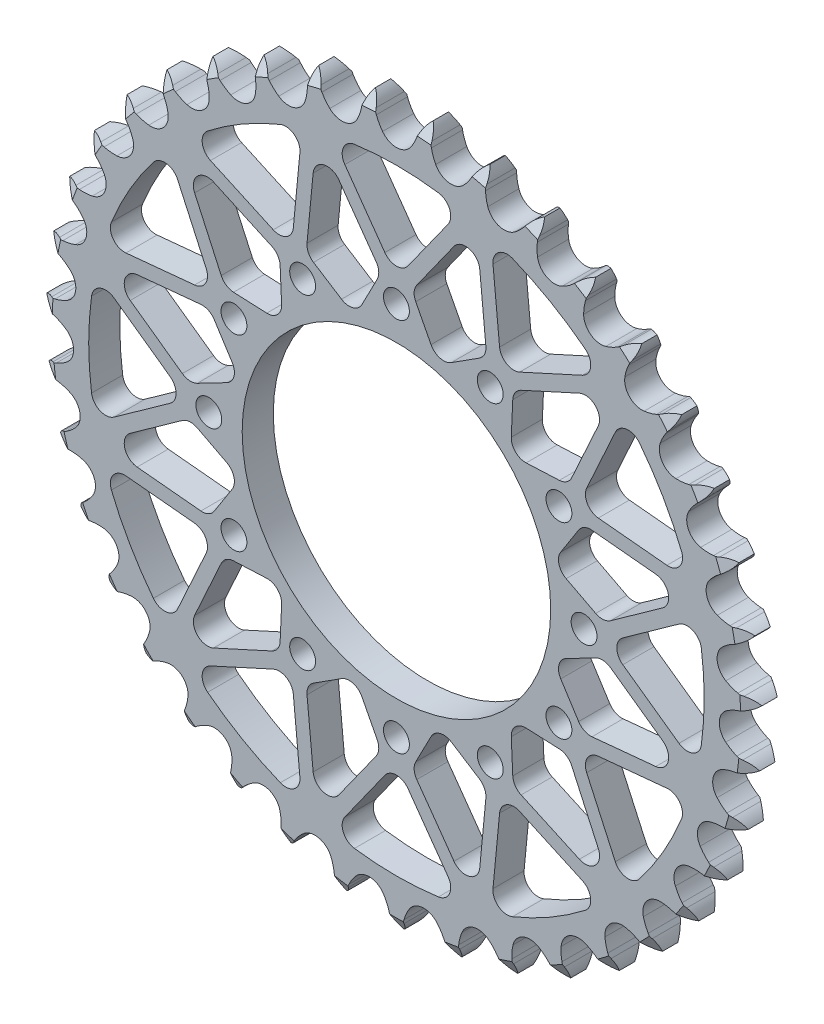
SolidWorks part; units mm, degrees
material "7075-T6 (SN)"
ref_plane "Front Plane" through (0, 0, 0) normal (0, 0, 1) x (1, 0, 0)
ref_plane "Top Plane" through (0, 0, 0) normal (0, 1, 0) x (1, 0, 0)
ref_plane "Right Plane" through (0, 0, 0) normal (1, 0, 0) x (0, 0, -1)
sketch "Work Sketch" plane through (0, 0, 0) normal (0, 0, 1) x (1, 0, 0)
  line L0 (0, 0) -> (0, 160.4542) construction
  line L1 (-112.0919, 78.9148) -> (87.2579, 78.9148) construction
  line L2 (5.102, 120.8822) -> (5.102, 112.9699) construction
  line L3 (-12.8497, 82.6953) -> (16.7256, 82.6953) construction
  line L4 (5.102, 82.6953) -> (-6.0879, 74.4036) construction
  line L5 (5.102, 82.6953) -> (-4.6505, 79.1506) construction
  line L6 (-4.6505, 79.1506) -> (-6.8863, 85.3019)
  line L7 (-11.5114, 78.0206) -> (-7.1525, 78.0206) construction
  line L8 (-11.0765, 124.7602) -> (-11.0765, 110.2345) construction
  line L9 (0, 0) -> (-3.4402, 42.6146) construction
  circle A0 centre (0, 0) radius 78.9148
  circle A1 centre (0, 78.9148) radius 4.0088
  arc A2 (-4.6505, 79.1506) -> (-3.2209, 76.5281) centre (5.0804, 82.7541) ccw
  circle A3 centre (-11.0765, 78.0206) radius 6.4254
  point P23 (-3.2209, 76.5281)
  dimension "D1" = 157.8295
  dimension "D8" = 10.3767
  dimension "D2" = 8.0177
  dimension "D3" = 5.102
  dimension "D4" = 3.7806
  dimension "D5" = 36.538
  dimension "D6" = 16.564
  dimension "D7" = 10.3767
  dimension "D9" = 0.8942
  dimension "D10" = 11.0765
  dimension "D11" = 4.615
sketch "Teeth Sketch" plane through (0, 0, 0) normal (0, 0, 1) x (1, 0, 0)
  line L0 (5.0376, 80.2155) -> (4.6505, 79.1506)
  line L1 (-7.4865, 92.7372) -> (-4.7839, 59.2593) construction
  line L2 (0, 0) -> (-10.9133, 132.3061) construction
  line L3 (7.8951, 79.9848) -> (8.1063, 78.8717)
  line L4 (16093.3137, -199351.4616) -> (-16096.7539, 199394.0762) construction
  line L5 (0, 146.3285) -> (0, 56.9858) construction
  line L6 (17.8398, 78.3686) -> (17.287, 77.3797)
  line L7 (0, -200000) -> (0, 200160.4542) construction
  line L8 (20.6234, 77.6826) -> (20.6533, 76.5499)
  line L9 (-4.6505, 79.1506) -> (-6.8863, 85.3019) construction
  line L10 (44.1616, 67.154) -> (43.8313, 66.0702)
  line L11 (-5.0376, 80.2155) -> (-4.6505, 79.1506)
  line L12 (30.18, 74.4921) -> (29.4757, 73.6046)
  line L13 (32.8175, 73.3684) -> (32.6653, 72.2456)
  line L14 (41.7385, 68.6862) -> (40.901, 67.9232)
  line L15 (52.2161, 61.1014) -> (51.267, 60.4826)
  line L16 (54.362, 59.2003) -> (53.8621, 58.1836)
  line L17 (61.3413, 51.9341) -> (60.3052, 51.4756)
  line L18 (63.1544, 49.7134) -> (62.4979, 48.79)
  line L19 (68.8777, 41.4218) -> (67.7815, 41.1354)
  line L20 (70.3112, 38.939) -> (69.515, 38.1328)
  line L21 (74.6303, 29.8366) -> (73.5023, 29.7298)
  line L22 (75.6469, 27.156) -> (74.7318, 26.488)
  line L23 (78.45, 17.4787) -> (77.3195, 17.5542)
  line L24 (79.0234, 14.6698) -> (78.013, 14.1572)
  line L25 (80.2378, 4.6681) -> (79.1341, 4.9239)
  line L26 (80.3533, 1.8035) -> (79.2737, 1.4597)
  line L27 (79.9476, -8.2634) -> (78.8992, -7.8338)
  line L28 (79.602, -11.1094) -> (78.4813, -11.2756)
  line L29 (77.5867, -20.9809) -> (76.6208, -20.3887)
  line L30 (76.7891, -23.7346) -> (75.6562, -23.7189)
  line L31 (73.2164, -33.155) -> (72.358, -32.4155)
  line L32 (71.9874, -35.7451) -> (70.8717, -35.5478)
  line L33 (66.9499, -44.4704) -> (66.2212, -43.6028)
  line L34 (65.3213, -46.8298) -> (64.2517, -46.4561)
  line L35 (58.9493, -54.634) -> (58.3693, -53.6608)
  line L36 (56.9634, -56.7016) -> (55.9676, -56.1612)
  line L37 (49.422, -63.3827) -> (49.0056, -62.329)
  line L38 (47.1301, -65.1049) -> (46.2339, -64.4118)
  line L39 (38.6147, -70.4897) -> (38.3727, -69.3829)
  line L40 (36.0763, -71.822) -> (35.3028, -70.9941)
  line L41 (26.8073, -75.7712) -> (26.746, -74.6398)
  line L42 (24.088, -76.679) -> (23.4574, -75.7377)
  line L43 (14.3056, -79.0901) -> (14.4266, -77.9636)
  line L44 (11.4759, -79.55) -> (11.0044, -78.5198)
  line L45 (1.4334, -80.3607) -> (1.7335, -79.2682)
  line L46 (-1.4334, -80.3607) -> (-1.7335, -79.2682)
  line L47 (-11.4759, -79.55) -> (-11.0044, -78.5198)
  line L48 (-14.3056, -79.0901) -> (-14.4266, -77.9636)
  line L49 (-24.088, -76.679) -> (-23.4574, -75.7377)
  line L50 (-26.8073, -75.7712) -> (-26.746, -74.6398)
  line L51 (-36.0763, -71.822) -> (-35.3028, -70.9941)
  line L52 (-38.6147, -70.4897) -> (-38.3727, -69.3829)
  line L53 (-47.1301, -65.1049) -> (-46.2339, -64.4118)
  line L54 (-49.422, -63.3827) -> (-49.0056, -62.329)
  line L55 (-56.9634, -56.7016) -> (-55.9676, -56.1612)
  line L56 (-58.9493, -54.634) -> (-58.3693, -53.6608)
  line L57 (-65.3213, -46.8298) -> (-64.2517, -46.4561)
  line L58 (-66.9499, -44.4704) -> (-66.2212, -43.6028)
  line L59 (-71.9874, -35.7451) -> (-70.8717, -35.5478)
  line L60 (-73.2164, -33.155) -> (-72.358, -32.4155)
  line L61 (-76.7891, -23.7346) -> (-75.6562, -23.7189)
  line L62 (-77.5867, -20.9809) -> (-76.6208, -20.3887)
  line L63 (-79.602, -11.1094) -> (-78.4813, -11.2756)
  line L64 (-79.9476, -8.2634) -> (-78.8992, -7.8338)
  line L65 (-80.3533, 1.8035) -> (-79.2737, 1.4597)
  line L66 (-80.2378, 4.6681) -> (-79.1341, 4.9239)
  line L67 (-79.0234, 14.6698) -> (-78.013, 14.1572)
  line L68 (-78.45, 17.4787) -> (-77.3195, 17.5542)
  line L69 (-75.6469, 27.156) -> (-74.7318, 26.488)
  line L70 (-74.6303, 29.8366) -> (-73.5023, 29.7298)
  line L71 (-70.3112, 38.939) -> (-69.515, 38.1328)
  line L72 (-68.8777, 41.4218) -> (-67.7815, 41.1354)
  line L73 (-63.1544, 49.7134) -> (-62.4979, 48.79)
  line L74 (-61.3413, 51.9341) -> (-60.3052, 51.4756)
  line L75 (-54.362, 59.2003) -> (-53.8621, 58.1836)
  line L76 (-52.2161, 61.1014) -> (-51.267, 60.4826)
  line L77 (-44.1616, 67.154) -> (-43.8313, 66.0702)
  line L78 (-41.7385, 68.6862) -> (-40.901, 67.9232)
  line L79 (-32.8175, 73.3684) -> (-32.6653, 72.2456)
  line L80 (-30.18, 74.4921) -> (-29.4757, 73.6046)
  line L81 (-20.6234, 77.6826) -> (-20.6533, 76.5499)
  line L82 (-17.8398, 78.3686) -> (-17.287, 77.3797)
  line L83 (-7.8951, 79.9848) -> (-8.1063, 78.8717)
  arc A0 (-6.8336, 82.8459) -> (-5.0376, 80.2155) centre (-11.0765, 78.0206) cw
  circle A1 centre (-11.0765, 78.0206) radius 6.4254 construction
  arc A2 (-3.2209, 76.5281) -> (-4.6505, 79.1506) centre (5.0804, 82.7541) cw
  arc A3 (-4.6505, 79.1506) -> (-3.2209, 76.5281) centre (5.0804, 82.7541) ccw construction
  circle A4 centre (0, 78.9148) radius 4.0088 construction
  arc A5 (-3.2209, 76.5281) -> (3.2209, 76.5281) centre (0, 78.9148) ccw
  arc A6 (3.2209, 76.5281) -> (4.6505, 79.1506) centre (-5.0804, 82.7541) ccw
  arc A7 (6.8336, 82.8459) -> (5.0376, 80.2155) centre (11.0765, 78.0206) ccw
  arc A8 (6.5443, 82.8692) -> (7.8951, 79.9848) centre (1.5824, 78.787) cw
  arc A9 (9.0967, 76.0537) -> (8.1063, 78.8717) centre (18.2893, 80.8676) cw
  arc A10 (9.0967, 76.0537) -> (15.4552, 75.0204) centre (12.6588, 77.8928) ccw
  arc A11 (15.4552, 75.0204) -> (17.287, 77.3797) centre (8.2601, 82.4975) ccw
  arc A12 (20.0345, 80.6769) -> (17.8398, 78.3686) centre (23.4484, 75.2334) ccw
  arc A13 (19.7528, 80.7463) -> (20.6234, 77.6826) centre (14.2002, 77.5129) cw
  arc A14 (21.1788, 73.6096) -> (20.6533, 76.5499) centre (31.0245, 76.8865) cw
  arc A15 (21.1788, 73.6096) -> (27.2892, 71.5697) centre (24.9898, 74.8535) ccw
  arc A16 (27.2892, 71.5697) -> (29.4757, 73.6046) centre (21.3867, 80.1041) ccw
  arc A17 (32.7165, 76.4184) -> (30.18, 74.4921) centre (35.2131, 70.4978) ccw
  arc A18 (32.4496, 76.5321) -> (32.8175, 73.3684) centre (26.4502, 74.2313) cw
  arc A19 (32.7124, 69.2591) -> (32.6653, 72.2456) centre (42.9562, 70.9142) cw
  arc A20 (32.7124, 69.2591) -> (38.4163, 66.2654) centre (36.6735, 69.8756) ccw
  arc A21 (38.4163, 66.2654) -> (40.901, 67.9232) centre (33.9593, 75.6361) ccw
  arc A22 (44.5512, 70.1807) -> (41.7385, 68.6862) centre (46.0657, 63.9363) ccw
  arc A23 (44.306, 70.3358) -> (44.1616, 67.154) centre (38.0153, 69.0271) cw
  arc A24 (43.3987, 63.1147) -> (43.8313, 66.0702) centre (53.7754, 63.1052) cw
  arc A25 (43.3987, 63.1147) -> (48.5486, 59.2448) centre (47.4074, 63.0878) ccw
  arc A26 (48.5486, 59.2448) -> (51.267, 60.4826) centre (45.6524, 69.2092) ccw
  arc A27 (55.2321, 62.1253) -> (52.2161, 61.1014) centre (55.7253, 55.7189) ccw
  arc A28 (55.0149, 62.3178) -> (54.362, 59.2003) centre (48.5957, 62.0351) cw
  arc A29 (52.961, 55.3358) -> (53.8621, 58.1836) centre (63.2018, 53.6618) cw
  arc A30 (52.961, 55.3358) -> (57.4234, 50.6899) centre (56.9135, 54.6662) ccw
  arc A31 (57.4234, 50.6899) -> (60.3052, 51.4756) centre (56.1632, 60.9898) ccw
  arc A32 (64.4824, 52.461) -> (61.3413, 51.9341) centre (63.9416, 46.0584) ccw
  arc A33 (64.2989, 52.6858) -> (63.1544, 49.7134) centre (57.9175, 53.4365) cw
  arc A34 (61.1517, 46.1237) -> (62.4979, 48.79) centre (70.9913, 42.8287) cw
  arc A35 (61.1517, 46.1237) -> (64.811, 40.8221) centre (64.9456, 44.8287) ccw
  arc A36 (64.811, 40.8221) -> (67.7815, 41.1354) centre (65.2193, 51.1908) ccw
  arc A37 (72.0627, 41.4379) -> (68.8777, 41.4218) centre (70.5018, 35.205) ccw
  arc A38 (71.9177, 41.6892) -> (70.3112, 38.939) centre (65.7393, 43.4539) cw
  arc A39 (67.7585, 35.717) -> (69.515, 38.1328) centre (76.9422, 30.8862) cw
  arc A40 (67.7585, 35.717) -> (70.5201, 29.8971) centre (71.2956, 33.8302) ccw
  arc A41 (70.5201, 29.8971) -> (73.5023, 29.7298) centre (72.5864, 40.0659) ccw
  arc A42 (77.7767, 29.3416) -> (74.6303, 29.8366) centre (75.2361, 23.4398) ccw
  arc A43 (77.6738, 29.6129) -> (75.6469, 27.156) centre (71.8585, 32.3458) cw
  arc A44 (72.6105, 24.3852) -> (74.7318, 26.488) centre (80.9003, 18.1439) cw
  arc A45 (72.6105, 24.3852) -> (74.4027, 18.1977) centre (75.7991, 21.9555) ccw
  arc A46 (74.4027, 18.1977) -> (77.3195, 17.5542) centre (78.0734, 27.9034) ccw
  arc A47 (81.4762, 16.4854) -> (78.45, 17.4787) centre (78.0218, 11.0675) ccw
  arc A48 (81.4182, 16.7697) -> (79.0234, 14.6698) centre (76.1166, 20.4) cw
  arc A49 (75.5818, 12.4219) -> (78.013, 14.1572) centre (82.7631, 4.9316) cw
  arc A50 (75.5818, 12.4219) -> (76.3583, 6.027) centre (78.3394, 9.5121) ccw
  arc A51 (76.3583, 6.027) -> (79.1341, 4.9239) centre (81.5384, 15.0182) ccw
  arc A52 (83.0656, 3.2022) -> (80.2378, 4.6681) centre (78.7868, -1.5914) ccw
  arc A53 (83.0539, 3.4922) -> (80.3533, 1.8035) centre (78.4033, 7.9259) cw
  arc A54 (76.5957, 0.1368) -> (79.2737, 1.4597) centre (82.4825, -8.4084) cw
  arc A55 (76.5957, 0.1368) -> (76.3363, -6.2998) centre (78.8508, -3.1776) ccw
  arc A56 (76.3363, -6.2998) -> (78.8992, -7.8338) centre (82.8916, 1.7441) ccw
  arc A57 (82.5035, -10.1639) -> (79.9476, -8.2634) centre (77.5113, -14.2091) ccw
  arc A58 (82.5385, -9.8758) -> (79.602, -11.1094) centre (78.6594, -4.7535) cw
  arc A59 (75.6257, -12.1517) -> (78.4813, -11.2756) centre (80.0655, -21.5307) cw
  arc A60 (75.6257, -12.1517) -> (74.3372, -18.4634) centre (77.3199, -15.785) ccw
  arc A61 (74.3372, -18.4634) -> (76.6208, -20.3887) centre (82.0979, -11.5753) ccw
  arc A62 (79.8047, -23.2668) -> (77.5867, -20.9809) centre (74.2283, -26.4587) ccw
  arc A63 (79.8855, -22.9881) -> (76.7891, -23.7346) centre (76.8783, -17.3098) cw
  arc A64 (72.6971, -24.1256) -> (75.6562, -23.7189) centre (75.5749, -34.0953) cw
  arc A65 (72.6971, -24.1256) -> (70.4128, -30.1488) centre (73.7866, -27.9836) ccw
  arc A66 (70.4128, -30.1488) -> (72.358, -32.4155) centre (79.178, -24.5948) ccw
  arc A67 (75.039, -35.7671) -> (73.2164, -33.155) centre (69.0227, -38.0232) ccw
  arc A68 (75.1634, -35.5049) -> (71.9874, -35.7451) centre (73.106, -29.4178) cw
  arc A69 (67.8857, -35.4746) -> (70.8717, -35.5478) centre (69.127, -45.7768) cw
  arc A70 (67.8857, -35.4746) -> (64.6648, -41.0534) centre (68.3422, -39.4574) ccw
  arc A71 (64.6648, -41.0534) -> (66.2212, -43.6028) centre (74.2074, -36.9773) ccw
  arc A72 (68.3299, -47.341) -> (66.9499, -44.4704) centre (62.0296, -48.6028) ccw
  arc A73 (68.4947, -47.1022) -> (65.3213, -46.8298) centre (67.4404, -40.7639) cw
  arc A74 (61.3161, -45.9049) -> (64.2517, -46.4561) centre (60.8887, -56.2728) cw
  arc A75 (61.3161, -45.9049) -> (57.2419, -50.8948) centre (61.1278, -49.9093) ccw
  arc A76 (57.2419, -50.8948) -> (58.3693, -53.6608) centre (67.3148, -48.4022) ccw
  arc A77 (59.851, -57.6888) -> (58.9493, -54.634) centre (53.4299, -57.9236) ccw
  arc A78 (60.052, -57.4796) -> (56.9634, -56.7016) centre (60.0281, -51.0542) cw
  arc A79 (53.1584, -55.1462) -> (55.9676, -56.1612) centre (51.0734, -65.3113) cw
  arc A80 (53.1584, -55.1462) -> (48.3366, -59.4179) centre (52.3302, -59.0685) ccw
  arc A81 (48.3366, -59.4179) -> (49.0056, -62.329) centre (58.6789, -58.5735) ccw
  arc A82 (49.822, -66.5425) -> (49.422, -63.3827) centre (43.4464, -65.7443) ccw
  arc A83 (50.054, -66.3682) -> (47.1301, -65.1049) centre (51.0611, -60.0222) cw
  arc A84 (43.6239, -62.9593) -> (46.2339, -64.4118) centre (39.9354, -72.6583) cw
  arc A85 (43.6239, -62.9593) -> (38.1793, -66.4022) centre (42.1772, -66.698) ccw
  arc A86 (38.1793, -66.4022) -> (38.3727, -69.3829) centre (48.5231, -67.2277) ccw
  arc A87 (38.5026, -73.6728) -> (38.6147, -70.4897) centre (32.3376, -71.8622) ccw
  arc A88 (38.7596, -73.538) -> (36.0763, -71.822) centre (40.7716, -67.4357) cw
  arc A89 (32.9596, -69.1417) -> (35.3028, -70.9941) centre (27.763, -78.1234) cw
  arc A90 (32.9596, -69.1417) -> (27.0333, -71.6667) centre (30.932, -72.6) ccw
  arc A91 (27.0333, -71.6667) -> (26.746, -74.6398) centre (37.1107, -74.1408) ccw
  arc A92 (26.1861, -78.8951) -> (26.8073, -75.7712) centre (20.3913, -76.1189) ccw
  arc A93 (26.4613, -78.8032) -> (24.088, -76.679) centre (29.4261, -73.1027) cw
  arc A94 (21.4417, -73.5335) -> (23.4574, -75.7377) centre (14.8716, -81.5653) cw
  arc A95 (21.4417, -73.5335) -> (15.187, -75.0751) centre (18.8855, -76.6216) ccw
  arc A96 (15.187, -75.0751) -> (14.4266, -77.9636) centre (24.7371, -79.1336) ccw
  arc A97 (13.1913, -82.0739) -> (14.3056, -79.0901) centre (7.9169, -78.4042) ccw
  arc A98 (13.4777, -82.0274) -> (11.4759, -79.55) centre (17.3186, -76.8763) cw
  arc A99 (9.3684, -76.0207) -> (11.0044, -78.5198) centre (1.595, -82.8946) cw
  arc A100 (9.3684, -76.0207) -> (2.9475, -76.5391) centre (6.35, -78.6589) ccw
  arc A101 (2.9475, -76.5391) -> (1.7335, -79.2682) centre (11.7228, -82.077) ccw
  arc A102 (-0.1451, -83.1271) -> (1.4334, -80.3607) centre (-4.7625, -78.6589) ccw
  arc A103 (0.1451, -83.1271) -> (-1.4334, -80.3607) centre (4.7625, -78.6589) cw
  arc A104 (-2.9475, -76.5391) -> (-1.7335, -79.2682) centre (-11.7228, -82.077) cw
  arc A105 (-2.9475, -76.5391) -> (-9.3684, -76.0207) centre (-6.35, -78.6589) ccw
  arc A106 (-9.3684, -76.0207) -> (-11.0044, -78.5198) centre (-1.595, -82.8946) ccw
  arc A107 (-13.4777, -82.0274) -> (-11.4759, -79.55) centre (-17.3186, -76.8763) ccw
  arc A108 (-13.1913, -82.0739) -> (-14.3056, -79.0901) centre (-7.9169, -78.4042) cw
  arc A109 (-15.187, -75.0751) -> (-14.4266, -77.9636) centre (-24.7371, -79.1336) cw
  arc A110 (-15.187, -75.0751) -> (-21.4417, -73.5335) centre (-18.8855, -76.6216) ccw
  arc A111 (-21.4417, -73.5335) -> (-23.4574, -75.7377) centre (-14.8716, -81.5653) ccw
  arc A112 (-26.4613, -78.8032) -> (-24.088, -76.679) centre (-29.4261, -73.1027) ccw
  arc A113 (-26.1861, -78.8951) -> (-26.8073, -75.7712) centre (-20.3913, -76.1189) cw
  arc A114 (-27.0333, -71.6667) -> (-26.746, -74.6398) centre (-37.1107, -74.1408) cw
  arc A115 (-27.0333, -71.6667) -> (-32.9596, -69.1417) centre (-30.932, -72.6) ccw
  arc A116 (-32.9596, -69.1417) -> (-35.3028, -70.9941) centre (-27.763, -78.1234) ccw
  arc A117 (-38.7596, -73.538) -> (-36.0763, -71.822) centre (-40.7716, -67.4357) ccw
  arc A118 (-38.5026, -73.6728) -> (-38.6147, -70.4897) centre (-32.3376, -71.8622) cw
  arc A119 (-38.1793, -66.4022) -> (-38.3727, -69.3829) centre (-48.5231, -67.2277) cw
  arc A120 (-38.1793, -66.4022) -> (-43.6239, -62.9593) centre (-42.1772, -66.698) ccw
  arc A121 (-43.6239, -62.9593) -> (-46.2339, -64.4118) centre (-39.9354, -72.6583) ccw
  arc A122 (-50.054, -66.3682) -> (-47.1301, -65.1049) centre (-51.0611, -60.0222) ccw
  arc A123 (-49.822, -66.5425) -> (-49.422, -63.3827) centre (-43.4464, -65.7443) cw
  arc A124 (-48.3366, -59.4179) -> (-49.0056, -62.329) centre (-58.6789, -58.5735) cw
  arc A125 (-48.3366, -59.4179) -> (-53.1584, -55.1462) centre (-52.3302, -59.0685) ccw
  arc A126 (-53.1584, -55.1462) -> (-55.9676, -56.1612) centre (-51.0734, -65.3113) ccw
  arc A127 (-60.052, -57.4796) -> (-56.9634, -56.7016) centre (-60.0281, -51.0542) ccw
  arc A128 (-59.851, -57.6888) -> (-58.9493, -54.634) centre (-53.4299, -57.9236) cw
  arc A129 (-57.2419, -50.8948) -> (-58.3693, -53.6608) centre (-67.3148, -48.4022) cw
  arc A130 (-57.2419, -50.8948) -> (-61.3161, -45.9049) centre (-61.1278, -49.9093) ccw
  arc A131 (-61.3161, -45.9049) -> (-64.2517, -46.4561) centre (-60.8887, -56.2728) ccw
  arc A132 (-68.4947, -47.1022) -> (-65.3213, -46.8298) centre (-67.4404, -40.7639) ccw
  arc A133 (-68.3299, -47.341) -> (-66.9499, -44.4704) centre (-62.0296, -48.6028) cw
  arc A134 (-64.6648, -41.0534) -> (-66.2212, -43.6028) centre (-74.2074, -36.9773) cw
  arc A135 (-64.6648, -41.0534) -> (-67.8857, -35.4746) centre (-68.3422, -39.4574) ccw
  arc A136 (-67.8857, -35.4746) -> (-70.8717, -35.5478) centre (-69.127, -45.7768) ccw
  arc A137 (-75.1634, -35.5049) -> (-71.9874, -35.7451) centre (-73.106, -29.4178) ccw
  arc A138 (-75.039, -35.7671) -> (-73.2164, -33.155) centre (-69.0227, -38.0232) cw
  arc A139 (-70.4128, -30.1488) -> (-72.358, -32.4155) centre (-79.178, -24.5948) cw
  arc A140 (-70.4128, -30.1488) -> (-72.6971, -24.1256) centre (-73.7866, -27.9836) ccw
  arc A141 (-72.6971, -24.1256) -> (-75.6562, -23.7189) centre (-75.5749, -34.0953) ccw
  arc A142 (-79.8855, -22.9881) -> (-76.7891, -23.7346) centre (-76.8783, -17.3098) ccw
  arc A143 (-79.8047, -23.2668) -> (-77.5867, -20.9809) centre (-74.2283, -26.4587) cw
  arc A144 (-74.3372, -18.4634) -> (-76.6208, -20.3887) centre (-82.0979, -11.5753) cw
  arc A145 (-74.3372, -18.4634) -> (-75.6257, -12.1517) centre (-77.3199, -15.785) ccw
  arc A146 (-75.6257, -12.1517) -> (-78.4813, -11.2756) centre (-80.0655, -21.5307) ccw
  arc A147 (-82.5385, -9.8758) -> (-79.602, -11.1094) centre (-78.6594, -4.7535) ccw
  arc A148 (-82.5035, -10.1639) -> (-79.9476, -8.2634) centre (-77.5113, -14.2091) cw
  arc A149 (-76.3363, -6.2998) -> (-78.8992, -7.8338) centre (-82.8916, 1.7441) cw
  arc A150 (-76.3363, -6.2998) -> (-76.5957, 0.1368) centre (-78.8508, -3.1776) ccw
  arc A151 (-76.5957, 0.1368) -> (-79.2737, 1.4597) centre (-82.4825, -8.4084) ccw
  arc A152 (-83.0539, 3.4922) -> (-80.3533, 1.8035) centre (-78.4033, 7.9259) ccw
  arc A153 (-83.0656, 3.2022) -> (-80.2378, 4.6681) centre (-78.7868, -1.5914) cw
  arc A154 (-76.3583, 6.027) -> (-79.1341, 4.9239) centre (-81.5384, 15.0182) cw
  arc A155 (-76.3583, 6.027) -> (-75.5818, 12.4219) centre (-78.3394, 9.5121) ccw
  arc A156 (-75.5818, 12.4219) -> (-78.013, 14.1572) centre (-82.7631, 4.9316) ccw
  arc A157 (-81.4182, 16.7697) -> (-79.0234, 14.6698) centre (-76.1166, 20.4) ccw
  arc A158 (-81.4762, 16.4854) -> (-78.45, 17.4787) centre (-78.0218, 11.0675) cw
  arc A159 (-74.4027, 18.1977) -> (-77.3195, 17.5542) centre (-78.0734, 27.9034) cw
  arc A160 (-74.4027, 18.1977) -> (-72.6105, 24.3852) centre (-75.7991, 21.9555) ccw
  arc A161 (-72.6105, 24.3852) -> (-74.7318, 26.488) centre (-80.9003, 18.1439) ccw
  arc A162 (-77.6738, 29.6129) -> (-75.6469, 27.156) centre (-71.8585, 32.3458) ccw
  arc A163 (-77.7767, 29.3416) -> (-74.6303, 29.8366) centre (-75.2361, 23.4398) cw
  arc A164 (-70.5201, 29.8971) -> (-73.5023, 29.7298) centre (-72.5864, 40.0659) cw
  arc A165 (-70.5201, 29.8971) -> (-67.7585, 35.717) centre (-71.2956, 33.8302) ccw
  arc A166 (-67.7585, 35.717) -> (-69.515, 38.1328) centre (-76.9422, 30.8862) ccw
  arc A167 (-71.9177, 41.6892) -> (-70.3112, 38.939) centre (-65.7393, 43.4539) ccw
  arc A168 (-72.0627, 41.4379) -> (-68.8777, 41.4218) centre (-70.5018, 35.205) cw
  arc A169 (-64.811, 40.8221) -> (-67.7815, 41.1354) centre (-65.2193, 51.1908) cw
  arc A170 (-64.811, 40.8221) -> (-61.1517, 46.1237) centre (-64.9456, 44.8287) ccw
  arc A171 (-61.1517, 46.1237) -> (-62.4979, 48.79) centre (-70.9913, 42.8287) ccw
  arc A172 (-64.2989, 52.6858) -> (-63.1544, 49.7134) centre (-57.9175, 53.4365) ccw
  arc A173 (-64.4824, 52.461) -> (-61.3413, 51.9341) centre (-63.9416, 46.0584) cw
  arc A174 (-57.4234, 50.6899) -> (-60.3052, 51.4756) centre (-56.1632, 60.9898) cw
  arc A175 (-57.4234, 50.6899) -> (-52.961, 55.3358) centre (-56.9135, 54.6662) ccw
  arc A176 (-52.961, 55.3358) -> (-53.8621, 58.1836) centre (-63.2018, 53.6618) ccw
  arc A177 (-55.0149, 62.3178) -> (-54.362, 59.2003) centre (-48.5957, 62.0351) ccw
  arc A178 (-55.2321, 62.1253) -> (-52.2161, 61.1014) centre (-55.7253, 55.7189) cw
  arc A179 (-48.5486, 59.2448) -> (-51.267, 60.4826) centre (-45.6524, 69.2092) cw
  arc A180 (-48.5486, 59.2448) -> (-43.3987, 63.1147) centre (-47.4074, 63.0878) ccw
  arc A181 (-43.3987, 63.1147) -> (-43.8313, 66.0702) centre (-53.7754, 63.1052) ccw
  arc A182 (-44.306, 70.3358) -> (-44.1616, 67.154) centre (-38.0153, 69.0271) ccw
  arc A183 (-44.5512, 70.1807) -> (-41.7385, 68.6862) centre (-46.0657, 63.9363) cw
  arc A184 (-38.4163, 66.2654) -> (-40.901, 67.9232) centre (-33.9593, 75.6361) cw
  arc A185 (-38.4163, 66.2654) -> (-32.7124, 69.2591) centre (-36.6735, 69.8756) ccw
  arc A186 (-32.7124, 69.2591) -> (-32.6653, 72.2456) centre (-42.9562, 70.9142) ccw
  arc A187 (-32.4496, 76.5321) -> (-32.8175, 73.3684) centre (-26.4502, 74.2313) ccw
  arc A188 (-32.7165, 76.4184) -> (-30.18, 74.4921) centre (-35.2131, 70.4978) cw
  arc A189 (-27.2892, 71.5697) -> (-29.4757, 73.6046) centre (-21.3867, 80.1041) cw
  arc A190 (-27.2892, 71.5697) -> (-21.1788, 73.6096) centre (-24.9898, 74.8535) ccw
  arc A191 (-21.1788, 73.6096) -> (-20.6533, 76.5499) centre (-31.0245, 76.8865) ccw
  arc A192 (-19.7528, 80.7463) -> (-20.6234, 77.6826) centre (-14.2002, 77.5129) ccw
  arc A193 (-20.0345, 80.6769) -> (-17.8398, 78.3686) centre (-23.4484, 75.2334) cw
  arc A194 (-15.4552, 75.0204) -> (-17.287, 77.3797) centre (-8.2601, 82.4975) cw
  arc A195 (-15.4552, 75.0204) -> (-9.0967, 76.0537) centre (-12.6588, 77.8928) ccw
  arc A196 (-9.0967, 76.0537) -> (-8.1063, 78.8717) centre (-18.2893, 80.8676) ccw
  arc A197 (-6.5443, 82.8692) -> (-7.8951, 79.9848) centre (-1.5824, 78.787) ccw
  point P77 (0, 0)
  dimension "D1" = 4.615
  dimension "D2" = 4.715
  dimension "D3" = 39
extrude "Extrusion" add sketch "Teeth Sketch" along normal blind 7.2136 contours A0 region at (0, 0, 0)
sketch "Sketch1" plane through (0, 0, 0) normal (0, 0, -1) x (-1, 0, 0)
  circle A0 centre (0, 0) radius 78.9443
  circle A1 centre (0, 0) radius 35.7643
  dimension "D1" = 43.18
extrude "Cut-Extrude" cut sketch "Sketch1" against normal through all both and the other way through all contours A1
ref_axis "Axis2" through (0, 0, -0.3607) along (0, 0, 1)
ref_axis "Axis1" [suppressed] through (0, 0, 7.2136) along (0, 0, -1)
ref_plane "Sprocket Center Plane" through (0, 0, 3.6068) normal (0, 0, 1) x (1, 0, 0)
sketch "Pitch Circle" plane through (0, 0, 3.6068) normal (0, 0, -1) x (-1, 0, 0)
  circle A0 centre (0, 0) radius 82.9531 construction
  dimension "D1" = 165.9063
sketch "Chain Pitch Circle" plane through (0, 0, 0) normal (0, 0, -1) x (-1, 0, 0)
  circle A0 centre (0, 0) radius 82.9531 construction
  dimension "D1" = 165.9063
ref_plane "Center Plane" through (0, 0, 3.6068) normal (0, 0, 1) x (1, 0, 0)
hole_wizard "Ø6.0mm Dowel Hole1" positions "Sketch7" profile "Sketch8" hole size "Ø6.0" standard "ANSI Metric" end condition through all
sketch "Sketch7" plane through (0, 0, 7.2136) normal (0, 0, 1) x (1, 0, 0)
  point P0 (-43.5, 0)
  dimension "D1" = 43.5
sketch "Sketch8" plane through (-43.5, 0, 7.2136) normal (1, 0, 0) x (0, -1, 0)
  line L0 (0, 0) -> (0, 7.2136)
  line L1 (0, 7.2136) -> (3, 7.2136)
  line L2 (3, 7.2136) -> (3, 0)
  line L5 (3, 0) -> (0, 0)
  line L11 (0, -6.35) -> (0, 107.95) construction
  dimension "Thru Hole Dia." = 6
  dimension "Thru Hole Depth" = 7.2136
pattern_circular "CirPattern1" count 12 over 360 about axis through (0, 0, 7.2136) along (0, 0, -1) of "Ø6.0mm Dowel Hole1" reverse direction yes
ref_plane "Plane1" through (0, 0, 3.6068) normal (0, 0, -1) x (-1, 0, 0)
sketch "Sketch9" plane through (0, 0, 0) normal (0, 0, 1) x (1, 0, 0)
  line L0 (-43.5, 0) -> (-71.3499, 0) construction
  line L1 (-69.7539, 15.0068) -> (-48.707, 0)
  line L2 (-69.7539, -15.0068) -> (-48.707, 0)
  line L11 (-43.5, 0) -> (-37.6721, 21.75) construction
  line L13 (-68.9187, 18.4667) -> (-36.1404, 9.6838) construction
  line L18 (-43.3252, 20.9264) -> (-36.1404, 9.6838)
  line L19 (-47.9839, 3.5399) -> (-36.1404, 9.6838)
  line L20 (-43.3252, 20.9264) -> (-68.9187, 18.4667)
  line L21 (-47.9839, 3.5399) -> (-68.9187, 18.4667)
  circle A0 centre (0, 0) radius 74.9059 construction
  arc A1 (-57.4234, 50.6899) -> (-52.961, 55.3358) centre (-56.9135, 54.6662) ccw construction
  circle A2 centre (-43.5, 0) radius 3 construction
  circle A3 centre (-43.5, 0) radius 5.207
  circle A4 centre (-37.6721, 21.75) radius 3 construction
  circle A6 centre (-37.6721, 21.75) radius 5.207
  circle A196 centre (0, 0) radius 71.3499
  circle A197 centre (0, 0) radius 35.7643 construction
  circle A198 centre (0, 0) radius 35.7643
  circle A199 centre (0, 0) radius 37.4153 construction
  point P17 (-40.5861, 10.875)
  dimension "D1" = 3.556
  dimension "D2" = 1.651
  dimension "D3" = 10.414
  dimension "D4" = 3.302
extrude "Cut-Extrude2" cut sketch "Sketch9" along normal through all contours L1 A196 L2 | L21 L19 L18 L20 region at (-63.4426, 0, 0) region at (-50.2379, 13.4612, 0)
fillet "Fillet2" radius 3.302 7 edges at (-68.9187, 18.4667, 3.6068) (-36.1404, 9.6838, 3.6068) (-47.9839, 3.5399, 3.6068) (-43.3252, 20.9264, 3.6068) (-69.7539, -15.0068, 3.6068) (-48.707, 0, 3.6068) (-69.7539, 15.0068, 3.6068)
pattern_circular "CirPattern3" count 12 over 360 about axis through (0, 0, 7.2136) along (0, 0, -1) of "Cut-Extrude2", "Fillet2"
sketch "Sketch14" plane through (0, 0, 7.2136) normal (0, 0, 1) x (1, 0, 0)
  line L0 (-46.191, -4.47) -> (-39.3483, -8.0197) construction
  line L1 (-38.2956, 5.9905) -> (-37.9766, 6.1559)
  line L2 (-43.5, 0) -> (-38.293, 0) construction
  line L3 (-38.2956, -5.9905) -> (-37.9766, -6.1559)
  line L4 (-30.1697, 24.3357) -> (-29.8108, 24.3195)
  line L5 (-36.1602, 13.9599) -> (-35.9667, 13.6571)
  line L6 (-13.9599, 36.1602) -> (-13.6571, 35.9667)
  line L7 (-24.3357, 30.1697) -> (-24.3195, 29.8108)
  line L8 (5.9905, 38.2956) -> (6.1559, 37.9766)
  line L9 (-5.9905, 38.2956) -> (-6.1559, 37.9766)
  line L10 (24.3357, 30.1697) -> (24.3195, 29.8108)
  line L11 (13.9599, 36.1602) -> (13.6571, 35.9667)
  line L12 (36.1602, 13.9599) -> (35.9667, 13.6571)
  line L13 (30.1697, 24.3357) -> (29.8108, 24.3195)
  line L14 (38.2956, -5.9905) -> (37.9766, -6.1559)
  line L15 (38.2956, 5.9905) -> (37.9766, 6.1559)
  line L16 (30.1697, -24.3357) -> (29.8108, -24.3195)
  line L17 (36.1602, -13.9599) -> (35.9667, -13.6571)
  line L18 (13.9599, -36.1602) -> (13.6571, -35.9667)
  line L19 (24.3357, -30.1697) -> (24.3195, -29.8108)
  line L20 (-5.9905, -38.2956) -> (-6.1559, -37.9766)
  line L21 (5.9905, -38.2956) -> (6.1559, -37.9766)
  line L22 (-24.3357, -30.1697) -> (-24.3195, -29.8108)
  line L23 (-13.9599, -36.1602) -> (-13.6571, -35.9667)
  line L24 (-36.1602, -13.9599) -> (-35.9667, -13.6571)
  line L25 (-30.1697, -24.3357) -> (-29.8108, -24.3195)
  arc A0 (-39.0014, -2.6222) -> (-39.0014, 2.6222) centre (-43.5, 0) ccw
  circle A1 centre (0, 0) radius 35.7643 construction
  arc A2 (-37.9766, -6.1559) -> (-39.0014, -2.6222) centre (-36.807, -3.9013) cw
  arc A3 (-38.2956, 5.9905) -> (-36.1602, 13.9599) centre (-40.8688, 10.9508) ccw
  arc A4 (-38.2956, 5.9905) -> (-36.1602, 13.9599) centre (-40.8688, 10.9508) ccw
  arc A5 (-37.9766, 6.1559) -> (-39.0014, 2.6222) centre (-36.807, 3.9013) ccw
  circle A6 centre (0, 0) radius 35.7643
  arc A7 (-30.1697, 24.3357) -> (-24.3357, 30.1697) centre (-29.918, 29.918) ccw
  arc A8 (-29.8108, 24.3195) -> (-32.4651, 21.7716) centre (-29.9252, 21.7821) ccw
  arc A9 (-35.0873, 17.2299) -> (-32.4651, 21.7716) centre (-37.6721, 21.75) ccw
  arc A10 (-35.9667, 13.6571) -> (-35.0873, 17.2299) centre (-33.8264, 15.0249) cw
  arc A11 (-13.9599, 36.1602) -> (-5.9905, 38.2956) centre (-10.9508, 40.8688) ccw
  arc A12 (-13.6571, 35.9667) -> (-17.2299, 35.0873) centre (-15.0249, 33.8264) ccw
  arc A13 (-21.7716, 32.4651) -> (-17.2299, 35.0873) centre (-21.75, 37.6721) ccw
  arc A14 (-24.3195, 29.8108) -> (-21.7716, 32.4651) centre (-21.7821, 29.9252) cw
  arc A15 (5.9905, 38.2956) -> (13.9599, 36.1602) centre (10.9508, 40.8688) ccw
  arc A16 (6.1559, 37.9766) -> (2.6222, 39.0014) centre (3.9013, 36.807) ccw
  arc A17 (-2.6222, 39.0014) -> (2.6222, 39.0014) centre (0, 43.5) ccw
  arc A18 (-6.1559, 37.9766) -> (-2.6222, 39.0014) centre (-3.9013, 36.807) cw
  arc A19 (24.3357, 30.1697) -> (30.1697, 24.3357) centre (29.918, 29.918) ccw
  arc A20 (24.3195, 29.8108) -> (21.7716, 32.4651) centre (21.7821, 29.9252) ccw
  arc A21 (17.2299, 35.0873) -> (21.7716, 32.4651) centre (21.75, 37.6721) ccw
  arc A22 (13.6571, 35.9667) -> (17.2299, 35.0873) centre (15.0249, 33.8264) cw
  arc A23 (36.1602, 13.9599) -> (38.2956, 5.9905) centre (40.8688, 10.9508) ccw
  arc A24 (35.9667, 13.6571) -> (35.0873, 17.2299) centre (33.8264, 15.0249) ccw
  arc A25 (32.4651, 21.7716) -> (35.0873, 17.2299) centre (37.6721, 21.75) ccw
  arc A26 (29.8108, 24.3195) -> (32.4651, 21.7716) centre (29.9252, 21.7821) cw
  arc A27 (38.2956, -5.9905) -> (36.1602, -13.9599) centre (40.8688, -10.9508) ccw
  arc A28 (37.9766, -6.1559) -> (39.0014, -2.6222) centre (36.807, -3.9013) ccw
  arc A29 (39.0014, 2.6222) -> (39.0014, -2.6222) centre (43.5, 0) ccw
  arc A30 (37.9766, 6.1559) -> (39.0014, 2.6222) centre (36.807, 3.9013) cw
  arc A31 (30.1697, -24.3357) -> (24.3357, -30.1697) centre (29.918, -29.918) ccw
  arc A32 (29.8108, -24.3195) -> (32.4651, -21.7716) centre (29.9252, -21.7821) ccw
  arc A33 (35.0873, -17.2299) -> (32.4651, -21.7716) centre (37.6721, -21.75) ccw
  arc A34 (35.9667, -13.6571) -> (35.0873, -17.2299) centre (33.8264, -15.0249) cw
  arc A35 (13.9599, -36.1602) -> (5.9905, -38.2956) centre (10.9508, -40.8688) ccw
  arc A36 (13.6571, -35.9667) -> (17.2299, -35.0873) centre (15.0249, -33.8264) ccw
  arc A37 (21.7716, -32.4651) -> (17.2299, -35.0873) centre (21.75, -37.6721) ccw
  arc A38 (24.3195, -29.8108) -> (21.7716, -32.4651) centre (21.7821, -29.9252) cw
  arc A39 (-5.9905, -38.2956) -> (-13.9599, -36.1602) centre (-10.9508, -40.8688) ccw
  arc A40 (-6.1559, -37.9766) -> (-2.6222, -39.0014) centre (-3.9013, -36.807) ccw
  arc A41 (2.6222, -39.0014) -> (-2.6222, -39.0014) centre (0, -43.5) ccw
  arc A42 (6.1559, -37.9766) -> (2.6222, -39.0014) centre (3.9013, -36.807) cw
  arc A43 (-24.3357, -30.1697) -> (-30.1697, -24.3357) centre (-29.918, -29.918) ccw
  arc A44 (-24.3195, -29.8108) -> (-21.7716, -32.4651) centre (-21.7821, -29.9252) ccw
  arc A45 (-17.2299, -35.0873) -> (-21.7716, -32.4651) centre (-21.75, -37.6721) ccw
  arc A46 (-13.6571, -35.9667) -> (-17.2299, -35.0873) centre (-15.0249, -33.8264) cw
  arc A47 (-36.1602, -13.9599) -> (-38.2956, -5.9905) centre (-40.8688, -10.9508) ccw
  arc A48 (-35.9667, -13.6571) -> (-35.0873, -17.2299) centre (-33.8264, -15.0249) ccw
  arc A49 (-32.4651, -21.7716) -> (-35.0873, -17.2299) centre (-37.6721, -21.75) ccw
  arc A50 (-29.8108, -24.3195) -> (-32.4651, -21.7716) centre (-29.9252, -21.7821) cw
  point P10 (-41.0188, -4.5778)
  point P16 (-41.0188, 4.5778)
  point P144 (0, 0)
  dimension "D2" = 2.54
  dimension "D1" = 2.286
  dimension "D3" = 12
extrude "Cut-Extrude7" [suppressed] cut sketch "Sketch14" against normal through all
sketch "Sketch15" plane through (0, 0, 0) normal (0, 0, -1) x (-1, 0, 0)
  line L9 (-38.264, 54.1071) -> (-28.7286, 49.7594)
  line L10 (-28.7286, 49.7594) -> (-27.7261, 60.1911)
  line L11 (-49.7594, 28.7286) -> (-54.1071, 38.264)
  line L12 (-60.1911, 27.7261) -> (-49.7594, 28.7286)
  line L13 (-49.7594, 28.7286) -> (-54.1071, 38.264)
  line L14 (-60.1911, 27.7261) -> (-49.7594, 28.7286)
  line L15 (-47.5649, 9.4801) -> (-43.4148, 11.633)
  line L16 (-54.9005, 14.7105) -> (-47.5649, 9.4801)
  line L17 (-45.9324, 15.5724) -> (-54.9005, 14.7105)
  line L18 (-43.4148, 11.633) -> (-45.9324, 15.5724)
  line L19 (-47.5649, 9.4801) -> (-43.4148, 11.633)
  line L20 (-54.9005, 14.7105) -> (-47.5649, 9.4801)
  line L21 (-45.9324, 15.5724) -> (-54.9005, 14.7105)
  line L22 (-43.4148, 11.633) -> (-45.9324, 15.5724)
  line L23 (-40.1899, 40.1899) -> (-36.4523, 31.9925)
  line L24 (-36.4523, 31.9925) -> (-31.7819, 31.7819)
  line L25 (-31.7819, 31.7819) -> (-31.9925, 36.4523)
  line L26 (-31.9925, 36.4523) -> (-40.1899, 40.1899)
  line L27 (-6.084, 65.9901) -> (0, 57.4573)
  line L28 (0, 57.4573) -> (6.084, 65.9901)
  line L29 (-14.7105, 54.9005) -> (-15.5724, 45.9324)
  line L30 (-15.5724, 45.9324) -> (-11.633, 43.4148)
  line L31 (-11.633, 43.4148) -> (-9.4801, 47.5649)
  line L32 (-9.4801, 47.5649) -> (-14.7105, 54.9005)
  line L33 (27.7261, 60.1911) -> (28.7286, 49.7594)
  line L34 (28.7286, 49.7594) -> (38.264, 54.1071)
  line L35 (14.7105, 54.9005) -> (9.4801, 47.5649)
  line L36 (9.4801, 47.5649) -> (11.633, 43.4148)
  line L37 (11.633, 43.4148) -> (15.5724, 45.9324)
  line L38 (15.5724, 45.9324) -> (14.7105, 54.9005)
  line L39 (54.1071, 38.264) -> (49.7594, 28.7286)
  line L40 (49.7594, 28.7286) -> (60.1911, 27.7261)
  line L41 (40.1899, 40.1899) -> (31.9925, 36.4523)
  line L42 (31.9925, 36.4523) -> (31.7819, 31.7819)
  line L43 (31.7819, 31.7819) -> (36.4523, 31.9925)
  line L44 (36.4523, 31.9925) -> (40.1899, 40.1899)
  line L45 (65.9901, 6.084) -> (57.4573, 0)
  line L46 (57.4573, 0) -> (65.9901, -6.084)
  line L47 (54.9005, 14.7105) -> (45.9324, 15.5724)
  line L48 (45.9324, 15.5724) -> (43.4148, 11.633)
  line L49 (43.4148, 11.633) -> (47.5649, 9.4801)
  line L50 (47.5649, 9.4801) -> (54.9005, 14.7105)
  line L51 (60.1911, -27.7261) -> (49.7594, -28.7286)
  line L52 (49.7594, -28.7286) -> (54.1071, -38.264)
  line L53 (54.9005, -14.7105) -> (47.5649, -9.4801)
  line L54 (47.5649, -9.4801) -> (43.4148, -11.633)
  line L55 (43.4148, -11.633) -> (45.9324, -15.5724)
  line L56 (45.9324, -15.5724) -> (54.9005, -14.7105)
  line L57 (38.264, -54.1071) -> (28.7286, -49.7594)
  line L58 (28.7286, -49.7594) -> (27.7261, -60.1911)
  line L59 (40.1899, -40.1899) -> (36.4523, -31.9925)
  line L60 (36.4523, -31.9925) -> (31.7819, -31.7819)
  line L61 (31.7819, -31.7819) -> (31.9925, -36.4523)
  line L62 (31.9925, -36.4523) -> (40.1899, -40.1899)
  line L63 (6.084, -65.9901) -> (0, -57.4573)
  line L64 (0, -57.4573) -> (-6.084, -65.9901)
  line L65 (14.7105, -54.9005) -> (15.5724, -45.9324)
  line L66 (15.5724, -45.9324) -> (11.633, -43.4148)
  line L67 (11.633, -43.4148) -> (9.4801, -47.5649)
  line L68 (9.4801, -47.5649) -> (14.7105, -54.9005)
  line L69 (-27.7261, -60.1911) -> (-28.7286, -49.7594)
  line L70 (-28.7286, -49.7594) -> (-38.264, -54.1071)
  line L71 (-14.7105, -54.9005) -> (-9.4801, -47.5649)
  line L72 (-9.4801, -47.5649) -> (-11.633, -43.4148)
  line L73 (-11.633, -43.4148) -> (-15.5724, -45.9324)
  line L74 (-15.5724, -45.9324) -> (-14.7105, -54.9005)
  line L75 (-54.1071, -38.264) -> (-49.7594, -28.7286)
  line L76 (-49.7594, -28.7286) -> (-60.1911, -27.7261)
  line L77 (-40.1899, -40.1899) -> (-31.9925, -36.4523)
  line L78 (-31.9925, -36.4523) -> (-31.7819, -31.7819)
  line L79 (-31.7819, -31.7819) -> (-36.4523, -31.9925)
  line L80 (-36.4523, -31.9925) -> (-40.1899, -40.1899)
  line L81 (-65.9901, -6.084) -> (-57.4573, 0)
  line L82 (-57.4573, 0) -> (-65.9901, 6.084)
  line L83 (-54.9005, -14.7105) -> (-45.9324, -15.5724)
  line L84 (-45.9324, -15.5724) -> (-43.4148, -11.633)
  line L85 (-43.4148, -11.633) -> (-47.5649, -9.4801)
  line L86 (-47.5649, -9.4801) -> (-54.9005, -14.7105)
  circle A13 centre (0, 0) radius 31.6425
  arc A18 (-27.7261, 60.1911) -> (-38.264, 54.1071) centre (0, 0) ccw
  arc A19 (6.084, 65.9901) -> (-6.084, 65.9901) centre (0, 0) ccw
  arc A20 (38.264, 54.1071) -> (27.7261, 60.1911) centre (0, 0) ccw
  arc A21 (60.1911, 27.7261) -> (54.1071, 38.264) centre (0, 0) ccw
  arc A22 (-54.1071, 38.264) -> (-60.1911, 27.7261) centre (0, 0) ccw
  arc A23 (-54.1071, 38.264) -> (-60.1911, 27.7261) centre (0, 0) ccw
  arc A24 (65.9901, -6.084) -> (65.9901, 6.084) centre (0, 0) ccw
  arc A25 (54.1071, -38.264) -> (60.1911, -27.7261) centre (0, 0) ccw
  arc A26 (27.7261, -60.1911) -> (38.264, -54.1071) centre (0, 0) ccw
  arc A27 (-6.084, -65.9901) -> (6.084, -65.9901) centre (0, 0) ccw
  arc A28 (-38.264, -54.1071) -> (-27.7261, -60.1911) centre (0, 0) ccw
  arc A29 (-60.1911, -27.7261) -> (-54.1071, -38.264) centre (0, 0) ccw
  arc A30 (-65.9901, 6.084) -> (-65.9901, -6.084) centre (0, 0) ccw
  point P3 (0, 0)
  point P28 (0, 0)
  point P123 (0, 0)
  dimension "D6" = 5.08
  dimension "D7" = 5.08
  dimension "D8" = 12
sketch "Sketch16" plane through (0, 0, 0) normal (0, 0, -1) x (-1, 0, 0)
  line L1 (88.9, 88.9) -> (-88.9, 88.9)
  line L2 (88.9, 88.9) -> (88.9, -88.9)
  line L3 (88.9, -88.9) -> (-88.9, -88.9)
  line L4 (-88.9, 88.9) -> (-88.9, -88.9)
  line L5 (88.9, 88.9) -> (-88.9, -88.9) construction
  line L6 (88.9, -88.9) -> (-88.9, 88.9) construction
  point P0 (0, 0)
  dimension "D1" = 177.8
  dimension "D2" = 177.8
sketch "Sketch17" plane through (0, 0, 0) normal (0, 0, -1) x (-1, 0, 0)
  line L0 (88.9, 88.9) -> (-88.9, -88.9) construction
  line L2 (88.9, -88.9) -> (-88.9, -88.9)
  line L3 (88.9, -88.9) -> (88.9, 88.9)
  line L4 (88.9, 88.9) -> (-88.9, 88.9)
  line L5 (-88.9, -88.9) -> (-88.9, 88.9)
  line L6 (88.9, -88.9) -> (-88.9, 88.9) construction
  line L7 (88.9, 88.9) -> (-88.9, -88.9) construction
  circle A0 centre (0, 0) radius 82.9722
sketch "Sketch21" plane through (0, 0, 7.2136) normal (0, 0, 1) x (1, 0, 0)
  arc A2 (-3.2209, 76.5281) -> (3.2209, 76.5281) centre (0, 78.9148) ccw construction
  arc A3 (6.6765, 82.7031) -> (5.0376, 80.2155) centre (11.0765, 78.0206) ccw construction
  arc A4 (3.2209, 76.5281) -> (4.6505, 79.1506) centre (-5.0804, 82.7541) ccw construction
  arc A5 (-5.0376, 80.2155) -> (-6.6765, 82.7031) centre (-11.0765, 78.0206) ccw construction
  arc A6 (-4.6505, 79.1506) -> (-3.2209, 76.5281) centre (5.0804, 82.7541) ccw construction
  spline S0 degree 3 poles (-6.6765, 82.7031) (-5.9219, 82.0275) (-5.2061, 80.8157) (-4.6311, 79.0281) (-3.5595, 76.6811) (-2.089, 74.9139) (0, 74.9059) knots 0 0 0 0 0.279448 0.385006 0.524509 1 1 1 1
  spline S1 degree 3 poles (6.6765, 82.7031) (5.9219, 82.0275) (5.2061, 80.8157) (4.6311, 79.0281) (3.5595, 76.6811) (2.089, 74.9139) (0, 74.9059) knots 0 0 0 0 0.279448 0.385006 0.524509 1 1 1 1
  spline S2 degree 3 poles (6.6765, 82.7031) (7.3129, 81.9152) (7.825, 80.6043) (8.1059, 78.7476) (8.7871, 76.2591) (9.9551, 74.2789) (12.0158, 73.9359) knots 0 0 0 0 0.279448 0.385006 0.524509 1 1 1 1
  spline S3 degree 3 poles (19.8565, 80.5611) (19.0034, 80.0153) (18.1025, 78.934) (17.2481, 77.2618) (15.814, 75.1171) (14.079, 73.6087) (12.0158, 73.9359) knots 0 0 0 0 0.279448 0.385006 0.524509 1 1 1 1
  spline S4 degree 3 poles (19.8565, 80.5611) (20.3583, 79.6813) (20.6535, 78.3052) (20.6329, 76.4275) (20.9061, 73.8621) (21.7413, 71.7201) (23.7203, 71.051) knots 0 0 0 0 0.279448 0.385006 0.524509 1 1 1 1
  spline S5 degree 3 poles (32.5223, 76.3327) (31.5926, 75.9308) (30.53, 75.008) (29.4184, 73.4945) (27.6588, 71.6077) (25.7043, 70.397) (23.7203, 71.051) knots 0 0 0 0 0.279448 0.385006 0.524509 1 1 1 1
  spline S6 degree 3 poles (32.5223, 76.3327) (32.8765, 75.3838) (32.9471, 73.9781) (32.6256, 72.1281) (32.4837, 69.552) (32.9645, 67.3038) (34.8105, 66.3259) knots 0 0 0 0 0.279448 0.385006 0.524509 1 1 1 1
  spline S7 degree 3 poles (44.3458, 70.1272) (43.3637, 69.8797) (42.1667, 69.1393) (40.8268, 67.8237) (38.7873, 66.2436) (36.664, 65.3621) (34.8105, 66.3259) knots 0 0 0 0 0.279448 0.385006 0.524509 1 1 1 1
  spline S8 degree 3 poles (44.3458, 70.1272) (44.5431, 69.1338) (44.3874, 67.7351) (43.7732, 65.9605) (43.2199, 63.4406) (43.3339, 61.1443) (44.9992, 59.883) knots 0 0 0 0 0.279448 0.385006 0.524509 1 1 1 1
  spline S9 degree 3 poles (55.0207, 62.1056) (54.0116, 62.0187) (52.7114, 61.48) (51.1778, 60.3963) (48.9113, 59.1638) (46.674, 58.6344) (44.9992, 59.883) knots 0 0 0 0 0.279448 0.385006 0.524509 1 1 1 1
  spline S10 degree 3 poles (55.0207, 62.1056) (55.0561, 61.0933) (54.678, 59.7377) (53.7872, 58.0846) (52.8368, 55.686) (52.581, 53.4013) (54.0223, 51.8892) knots 0 0 0 0 0.279448 0.385006 0.524509 1 1 1 1
  spline S11 degree 3 poles (64.2706, 52.4754) (63.2607, 52.5515) (61.8909, 52.2283) (60.2033, 51.4047) (57.7684, 50.5517) (55.4752, 50.3881) (54.0223, 51.8892) knots 0 0 0 0 0.279448 0.385006 0.524509 1 1 1 1
  spline S12 degree 3 poles (64.2706, 52.4754) (64.1432, 51.4706) (63.5526, 50.1931) (62.4081, 48.7044) (61.0853, 46.4893) (60.4662, 44.2752) (61.6464, 42.5514) knots 0 0 0 0 0.279448 0.385006 0.524509 1 1 1 1
  spline S13 degree 3 poles (71.856, 41.4861) (70.8713, 41.7233) (69.4674, 41.624) (67.6696, 41.0818) (65.1294, 40.6304) (62.8396, 40.8367) (61.6464, 42.5514) knots 0 0 0 0 0.279448 0.385006 0.524509 1 1 1 1
  spline S14 degree 3 poles (71.856, 41.4861) (71.5691, 40.5147) (70.7811, 39.3486) (69.4126, 38.0627) (67.7517, 36.0885) (66.7854, 34.0023) (67.6738, 32.1116) knots 0 0 0 0 0.279448 0.385006 0.524509 1 1 1 1
  spline S15 degree 3 poles (77.5803, 29.4223) (76.6464, 29.8144) (75.2448, 29.9416) (73.3833, 29.6948) (70.8036, 29.6568) (68.5765, 30.2277) (67.6738, 32.1116) knots 0 0 0 0 0.279448 0.385006 0.524509 1 1 1 1
  spline S16 degree 3 poles (77.5803, 29.4223) (77.1413, 28.5096) (76.1765, 27.4849) (74.6195, 26.4352) (72.6633, 24.753) (71.3749, 22.8489) (71.9485, 20.8401) knots 0 0 0 0 0.279448 0.385006 0.524509 1 1 1 1
  spline S17 degree 3 poles (81.2953, 16.5966) (80.4364, 17.1334) (79.0734, 17.4837) (77.1964, 17.5388) (74.644, 17.915) (72.5373, 18.8358) (71.9485, 20.8401) knots 0 0 0 0 0.279448 0.385006 0.524509 1 1 1 1
  spline S18 degree 3 poles (81.2953, 16.5966) (80.7156, 15.7661) (79.5989, 14.9094) (77.8937, 14.1231) (75.693, 12.7765) (74.1159, 11.1037) (74.3598, 9.0289) knots 0 0 0 0 0.279448 0.385006 0.524509 1 1 1 1
  spline S19 degree 3 poles (82.9049, 3.341) (82.1432, 4.0086) (80.854, 4.5731) (79.0101, 4.9285) (76.5511, 5.7093) (74.6195, 6.9561) (74.3598, 9.0289) knots 0 0 0 0 0.279448 0.385006 0.524509 1 1 1 1
  spline S20 degree 3 poles (82.9049, 3.341) (82.1994, 2.6142) (80.9598, 1.9478) (79.1505, 1.4452) (76.7623, 0.469) (74.9372, -0.9292) (74.8452, -3.0162) knots 0 0 0 0 0.279448 0.385006 0.524509 1 1 1 1
  spline S21 degree 3 poles (82.3672, -10.0012) (81.7225, -9.22) (80.5405, -8.456) (78.7775, -7.8095) (76.4756, -6.6443) (74.769, -5.1038) (74.8452, -3.0162) knots 0 0 0 0 0.279448 0.385006 0.524509 1 1 1 1
  spline S22 degree 3 poles (82.3672, -10.0012) (81.5543, -10.6054) (80.2238, -11.0643) (78.3573, -11.2702) (75.8435, -11.8506) (73.8178, -12.9379) (73.3921, -14.9831) knots 0 0 0 0 0.279448 0.385006 0.524509 1 1 1 1
  spline S23 degree 3 poles (79.6963, -23.0843) (79.1852, -22.2098) (78.1411, -21.2661) (76.5046, -20.3451) (74.4195, -18.8258) (72.9821, -17.0315) (73.3921, -14.9831) knots 0 0 0 0 0.279448 0.385006 0.524509 1 1 1 1
  spline S24 degree 3 poles (79.6963, -23.0843) (78.7969, -23.5502) (77.4101, -23.7898) (75.5347, -23.6936) (72.9603, -23.8633) (70.7865, -24.6116) (70.0383, -26.562) knots 0 0 0 0 0.279448 0.385006 0.524509 1 1 1 1
  spline S25 degree 3 poles (74.9612, -35.5695) (74.5971, -34.6244) (73.7178, -33.5255) (72.2503, -32.3539) (70.4359, -30.5197) (69.3049, -28.5181) (70.0383, -26.562) knots 0 0 0 0 0.279448 0.385006 0.524509 1 1 1 1
  spline S26 degree 3 poles (74.9612, -35.5695) (73.9988, -35.8852) (72.5915, -35.8992) (70.7559, -35.5034) (68.1876, -35.2579) (65.9218, -35.6478) (64.8704, -37.453) knots 0 0 0 0 0.279448 0.385006 0.524509 1 1 1 1
  spline S27 degree 3 poles (68.2847, -47.1336) (68.0769, -46.1423) (67.3854, -44.9165) (66.1248, -43.5247) (64.628, -41.4232) (63.8328, -39.2661) (64.8704, -37.453) knots 0 0 0 0 0.279448 0.385006 0.524509 1 1 1 1
  spline S28 degree 3 poles (68.2847, -47.1336) (67.2842, -47.2907) (65.8928, -47.0788) (64.1445, -46.3937) (61.6488, -45.7394) (59.3499, -45.7608) (58.0225, -47.3739) knots 0 0 0 0 0.279448 0.385006 0.524509 1 1 1 1
  spline S29 degree 3 poles (59.8397, -57.4768) (59.7936, -56.465) (59.3076, -55.1442) (58.2866, -53.5682) (57.1464, -51.2539) (56.7075, -48.9971) (58.0225, -47.3739) knots 0 0 0 0 0.279448 0.385006 0.524509 1 1 1 1
  spline S30 degree 3 poles (59.8397, -57.4768) (58.8269, -57.4715) (57.4876, -57.0391) (55.8717, -56.0824) (53.5134, -55.0362) (51.2407, -54.6886) (49.6718, -56.0679) knots 0 0 0 0 0.279448 0.385006 0.524509 1 1 1 1
  spline S31 degree 3 poles (49.8449, -66.3315) (49.9616, -65.3254) (49.6938, -63.9437) (48.9389, -62.2243) (48.1846, -59.7571) (48.1134, -57.4591) (49.6718, -56.0679) knots 0 0 0 0 0.279448 0.385006 0.524509 1 1 1 1
  spline S32 degree 3 poles (49.8449, -66.3315) (48.846, -66.1637) (47.5934, -65.5221) (46.152, -64.3186) (43.9919, -62.9077) (41.8045, -62.2) (40.0347, -63.3097) knots 0 0 0 0 0.279448 0.385006 0.524509 1 1 1 1
  spline S33 degree 3 poles (38.5591, -73.4682) (38.8357, -72.4939) (38.793, -71.0871) (38.3237, -69.2689) (37.975, -66.7126) (38.2733, -64.433) (40.0347, -63.3097) knots 0 0 0 0 0.279448 0.385006 0.524509 1 1 1 1
  spline S34 degree 3 poles (38.5591, -73.4682) (37.6001, -73.1424) (36.4666, -72.3081) (35.2369, -70.889) (33.3312, -69.1498) (31.2856, -68.1004) (29.3606, -68.9119) knots 0 0 0 0 0.279448 0.385006 0.524509 1 1 1 1
  spline S35 degree 3 poles (26.2746, -78.7021) (26.704, -77.7848) (26.8875, -76.3894) (26.7159, -74.5194) (26.7817, -71.9403) (27.4419, -69.7381) (29.3606, -68.9119) knots 0 0 0 0 0.279448 0.385006 0.524509 1 1 1 1
  spline S36 degree 3 poles (26.2746, -78.7021) (25.3803, -78.2267) (24.3953, -77.2214) (23.4092, -75.6234) (21.8071, -73.6011) (19.9564, -72.2371) (17.9262, -72.7293) knots 0 0 0 0 0.279448 0.385006 0.524509 1 1 1 1
  spline S37 degree 3 poles (13.3097, -81.8977) (13.8806, -81.0611) (14.2856, -79.7132) (14.4161, -77.84) (14.8949, -75.3048) (15.8997, -73.237) (17.9262, -72.7293) knots 0 0 0 0 0.279448 0.385006 0.524509 1 1 1 1
  spline S38 degree 3 poles (13.3097, -81.8977) (12.5032, -81.285) (11.6922, -80.1347) (10.9752, -78.3992) (9.7183, -76.1461) (8.1103, -74.5029) (6.0274, -74.663) knots 0 0 0 0 0.279448 0.385006 0.524509 1 1 1 1
  spline S39 degree 3 poles (0, -82.9722) (0.6978, -82.238) (1.3137, -80.9725) (1.7431, -79.1445) (2.6223, -76.7189) (3.9458, -74.8391) (6.0274, -74.663) knots 0 0 0 0 0.279448 0.385006 0.524509 1 1 1 1
  spline S40 degree 3 poles (0, -82.9722) (-0.6978, -82.238) (-1.3137, -80.9725) (-1.7431, -79.1445) (-2.6223, -76.7189) (-3.9458, -74.8391) (-6.0274, -74.663) knots 0 0 0 0 0.279448 0.385006 0.524509 1 1 1 1
  spline S41 degree 3 poles (-13.3097, -81.8977) (-12.5032, -81.285) (-11.6922, -80.1347) (-10.9752, -78.3992) (-9.7183, -76.1461) (-8.1103, -74.5029) (-6.0274, -74.663) knots 0 0 0 0 0.279448 0.385006 0.524509 1 1 1 1
  spline S42 degree 3 poles (-13.3097, -81.8977) (-13.8806, -81.0611) (-14.2856, -79.7132) (-14.4161, -77.84) (-14.8949, -75.3048) (-15.8997, -73.237) (-17.9262, -72.7293) knots 0 0 0 0 0.279448 0.385006 0.524509 1 1 1 1
  spline S43 degree 3 poles (-26.2746, -78.7021) (-25.3803, -78.2267) (-24.3953, -77.2214) (-23.4092, -75.6234) (-21.8071, -73.6011) (-19.9564, -72.2371) (-17.9262, -72.7293) knots 0 0 0 0 0.279448 0.385006 0.524509 1 1 1 1
  spline S44 degree 3 poles (-26.2746, -78.7021) (-26.704, -77.7848) (-26.8875, -76.3894) (-26.7159, -74.5194) (-26.7817, -71.9403) (-27.4419, -69.7381) (-29.3606, -68.9119) knots 0 0 0 0 0.279448 0.385006 0.524509 1 1 1 1
  spline S45 degree 3 poles (-38.5591, -73.4682) (-37.6001, -73.1424) (-36.4666, -72.3081) (-35.2369, -70.889) (-33.3312, -69.1498) (-31.2856, -68.1004) (-29.3606, -68.9119) knots 0 0 0 0 0.279448 0.385006 0.524509 1 1 1 1
  spline S46 degree 3 poles (-38.5591, -73.4682) (-38.8357, -72.4939) (-38.793, -71.0871) (-38.3237, -69.2689) (-37.975, -66.7126) (-38.2733, -64.433) (-40.0347, -63.3097) knots 0 0 0 0 0.279448 0.385006 0.524509 1 1 1 1
  spline S47 degree 3 poles (-49.8449, -66.3315) (-48.846, -66.1637) (-47.5934, -65.5221) (-46.152, -64.3186) (-43.9919, -62.9077) (-41.8045, -62.2) (-40.0347, -63.3097) knots 0 0 0 0 0.279448 0.385006 0.524509 1 1 1 1
  spline S48 degree 3 poles (-49.8449, -66.3315) (-49.9616, -65.3254) (-49.6938, -63.9437) (-48.9389, -62.2243) (-48.1846, -59.7571) (-48.1134, -57.4591) (-49.6718, -56.0679) knots 0 0 0 0 0.279448 0.385006 0.524509 1 1 1 1
  spline S49 degree 3 poles (-59.8397, -57.4768) (-58.8269, -57.4715) (-57.4876, -57.0391) (-55.8717, -56.0824) (-53.5134, -55.0362) (-51.2407, -54.6886) (-49.6718, -56.0679) knots 0 0 0 0 0.279448 0.385006 0.524509 1 1 1 1
  spline S50 degree 3 poles (-59.8397, -57.4768) (-59.7936, -56.465) (-59.3076, -55.1442) (-58.2866, -53.5682) (-57.1464, -51.2539) (-56.7075, -48.9971) (-58.0225, -47.3739) knots 0 0 0 0 0.279448 0.385006 0.524509 1 1 1 1
  spline S51 degree 3 poles (-68.2847, -47.1336) (-67.2842, -47.2907) (-65.8928, -47.0788) (-64.1445, -46.3937) (-61.6488, -45.7394) (-59.3499, -45.7608) (-58.0225, -47.3739) knots 0 0 0 0 0.279448 0.385006 0.524509 1 1 1 1
  spline S52 degree 3 poles (-68.2847, -47.1336) (-68.0769, -46.1423) (-67.3854, -44.9165) (-66.1248, -43.5247) (-64.628, -41.4232) (-63.8328, -39.2661) (-64.8704, -37.453) knots 0 0 0 0 0.279448 0.385006 0.524509 1 1 1 1
  spline S53 degree 3 poles (-74.9612, -35.5695) (-73.9988, -35.8852) (-72.5915, -35.8992) (-70.7559, -35.5034) (-68.1876, -35.2579) (-65.9218, -35.6478) (-64.8704, -37.453) knots 0 0 0 0 0.279448 0.385006 0.524509 1 1 1 1
  spline S54 degree 3 poles (-74.9612, -35.5695) (-74.5971, -34.6244) (-73.7178, -33.5255) (-72.2503, -32.3539) (-70.4359, -30.5197) (-69.3049, -28.5181) (-70.0383, -26.562) knots 0 0 0 0 0.279448 0.385006 0.524509 1 1 1 1
  spline S55 degree 3 poles (-79.6963, -23.0843) (-78.7969, -23.5502) (-77.4101, -23.7898) (-75.5347, -23.6936) (-72.9603, -23.8633) (-70.7865, -24.6116) (-70.0383, -26.562) knots 0 0 0 0 0.279448 0.385006 0.524509 1 1 1 1
  spline S56 degree 3 poles (-79.6963, -23.0843) (-79.1852, -22.2098) (-78.1411, -21.2661) (-76.5046, -20.3451) (-74.4195, -18.8258) (-72.9821, -17.0315) (-73.3921, -14.9831) knots 0 0 0 0 0.279448 0.385006 0.524509 1 1 1 1
  spline S57 degree 3 poles (-82.3672, -10.0012) (-81.5543, -10.6054) (-80.2238, -11.0643) (-78.3573, -11.2702) (-75.8435, -11.8506) (-73.8178, -12.9379) (-73.3921, -14.9831) knots 0 0 0 0 0.279448 0.385006 0.524509 1 1 1 1
  spline S58 degree 3 poles (-82.3672, -10.0012) (-81.7225, -9.22) (-80.5405, -8.456) (-78.7775, -7.8095) (-76.4756, -6.6443) (-74.769, -5.1038) (-74.8452, -3.0162) knots 0 0 0 0 0.279448 0.385006 0.524509 1 1 1 1
  spline S59 degree 3 poles (-82.9049, 3.341) (-82.1994, 2.6142) (-80.9598, 1.9478) (-79.1505, 1.4452) (-76.7623, 0.469) (-74.9372, -0.9292) (-74.8452, -3.0162) knots 0 0 0 0 0.279448 0.385006 0.524509 1 1 1 1
  spline S60 degree 3 poles (-82.9049, 3.341) (-82.1432, 4.0086) (-80.854, 4.5731) (-79.0101, 4.9285) (-76.5511, 5.7093) (-74.6195, 6.9561) (-74.3598, 9.0289) knots 0 0 0 0 0.279448 0.385006 0.524509 1 1 1 1
  spline S61 degree 3 poles (-81.2953, 16.5966) (-80.7156, 15.7661) (-79.5989, 14.9094) (-77.8937, 14.1231) (-75.693, 12.7765) (-74.1159, 11.1037) (-74.3598, 9.0289) knots 0 0 0 0 0.279448 0.385006 0.524509 1 1 1 1
  spline S62 degree 3 poles (-81.2953, 16.5966) (-80.4364, 17.1334) (-79.0734, 17.4837) (-77.1964, 17.5388) (-74.644, 17.915) (-72.5373, 18.8358) (-71.9485, 20.8401) knots 0 0 0 0 0.279448 0.385006 0.524509 1 1 1 1
  spline S63 degree 3 poles (-77.5803, 29.4223) (-77.1413, 28.5096) (-76.1765, 27.4849) (-74.6195, 26.4352) (-72.6633, 24.753) (-71.3749, 22.8489) (-71.9485, 20.8401) knots 0 0 0 0 0.279448 0.385006 0.524509 1 1 1 1
  spline S64 degree 3 poles (-77.5803, 29.4223) (-76.6464, 29.8144) (-75.2448, 29.9416) (-73.3833, 29.6948) (-70.8036, 29.6568) (-68.5765, 30.2277) (-67.6738, 32.1116) knots 0 0 0 0 0.279448 0.385006 0.524509 1 1 1 1
  spline S65 degree 3 poles (-71.856, 41.4861) (-71.5691, 40.5147) (-70.7811, 39.3486) (-69.4126, 38.0627) (-67.7517, 36.0885) (-66.7854, 34.0023) (-67.6738, 32.1116) knots 0 0 0 0 0.279448 0.385006 0.524509 1 1 1 1
  spline S66 degree 3 poles (-71.856, 41.4861) (-70.8713, 41.7233) (-69.4674, 41.624) (-67.6696, 41.0818) (-65.1294, 40.6304) (-62.8396, 40.8367) (-61.6464, 42.5514) knots 0 0 0 0 0.279448 0.385006 0.524509 1 1 1 1
  spline S67 degree 3 poles (-64.2706, 52.4754) (-64.1432, 51.4706) (-63.5526, 50.1931) (-62.4081, 48.7044) (-61.0853, 46.4893) (-60.4662, 44.2752) (-61.6464, 42.5514) knots 0 0 0 0 0.279448 0.385006 0.524509 1 1 1 1
  spline S68 degree 3 poles (-64.2706, 52.4754) (-63.2607, 52.5515) (-61.8909, 52.2283) (-60.2033, 51.4047) (-57.7684, 50.5517) (-55.4752, 50.3881) (-54.0223, 51.8892) knots 0 0 0 0 0.279448 0.385006 0.524509 1 1 1 1
  spline S69 degree 3 poles (-55.0207, 62.1056) (-55.0561, 61.0933) (-54.678, 59.7377) (-53.7872, 58.0846) (-52.8368, 55.686) (-52.581, 53.4013) (-54.0223, 51.8892) knots 0 0 0 0 0.279448 0.385006 0.524509 1 1 1 1
  spline S70 degree 3 poles (-55.0207, 62.1056) (-54.0116, 62.0187) (-52.7114, 61.48) (-51.1778, 60.3963) (-48.9113, 59.1638) (-46.674, 58.6344) (-44.9992, 59.883) knots 0 0 0 0 0.279448 0.385006 0.524509 1 1 1 1
  spline S71 degree 3 poles (-44.3458, 70.1272) (-44.5431, 69.1338) (-44.3874, 67.7351) (-43.7732, 65.9605) (-43.2199, 63.4406) (-43.3339, 61.1443) (-44.9992, 59.883) knots 0 0 0 0 0.279448 0.385006 0.524509 1 1 1 1
  spline S72 degree 3 poles (-44.3458, 70.1272) (-43.3637, 69.8797) (-42.1667, 69.1393) (-40.8268, 67.8237) (-38.7873, 66.2436) (-36.664, 65.3621) (-34.8105, 66.3259) knots 0 0 0 0 0.279448 0.385006 0.524509 1 1 1 1
  spline S73 degree 3 poles (-32.5223, 76.3327) (-32.8765, 75.3838) (-32.9471, 73.9781) (-32.6256, 72.1281) (-32.4837, 69.552) (-32.9645, 67.3038) (-34.8105, 66.3259) knots 0 0 0 0 0.279448 0.385006 0.524509 1 1 1 1
  spline S74 degree 3 poles (-32.5223, 76.3327) (-31.5926, 75.9308) (-30.53, 75.008) (-29.4184, 73.4945) (-27.6588, 71.6077) (-25.7043, 70.397) (-23.7203, 71.051) knots 0 0 0 0 0.279448 0.385006 0.524509 1 1 1 1
  spline S75 degree 3 poles (-19.8565, 80.5611) (-20.3583, 79.6813) (-20.6535, 78.3052) (-20.6329, 76.4275) (-20.9061, 73.8621) (-21.7413, 71.7201) (-23.7203, 71.051) knots 0 0 0 0 0.279448 0.385006 0.524509 1 1 1 1
  spline S76 degree 3 poles (-19.8565, 80.5611) (-19.0034, 80.0153) (-18.1025, 78.934) (-17.2481, 77.2618) (-15.814, 75.1171) (-14.079, 73.6087) (-12.0158, 73.9359) knots 0 0 0 0 0.279448 0.385006 0.524509 1 1 1 1
  spline S77 degree 3 poles (-6.6765, 82.7031) (-7.3129, 81.9152) (-7.825, 80.6043) (-8.1059, 78.7476) (-8.7871, 76.2591) (-9.9551, 74.2789) (-12.0158, 73.9359) knots 0 0 0 0 0.279448 0.385006 0.524509 1 1 1 1
  point P534 (0, 0)
sketch "Sketch18" plane through (0, 0, 0) normal (1, 0, 0) x (0, 0, -1)
  line L0 (-1.8288, -82.9722) -> (-5.3848, -82.9722)
  line L1 (-5.3848, -82.9722) -> (-5.3848, -79.7786)
  line L2 (-5.3848, -79.7786) -> (-7.2136, -79.7786)
  line L3 (-7.2136, -79.7786) -> (-5.3848, -82.9722)
  line L4 (-7.2136, -79.7786) -> (-7.2136, -82.9722)
  line L5 (-7.2136, -82.9722) -> (-5.3848, -82.9722)
  line L6 (-7.2136, -79.7786) -> (-7.2136, -82.9722)
  line L7 (-5.3848, -82.9722) -> (-7.2136, -79.7786)
  dimension "D1" = 3.556
  dimension "D2" = 3.1936
  dimension "D3" = 1.8288
revolve "Cut-Revolve2" cut sketch "Sketch18" angle 360 about axis through (0, 0, -0.3607) along (0, 0, 1) region at (0, -81.9076, 6.604)
mirror "Mirror1" about plane through (0, 0, 3.6068) normal (0, 0, -1) of "Cut-Revolve2"
sketch "Sketch23" plane through (0, 0, 0) normal (1, 0, 0) x (0, 0, -1)
  line L0 (-7.2136, 0.1368) -> (0, 0.1368) construction
  line L1 (-13.1318, -82.9722) -> (5.9182, -82.9722)
  line L2 (-13.1318, -82.9722) -> (-13.1318, 83.2458)
  line L3 (-13.1318, 83.2458) -> (5.9182, 83.2458)
  line L4 (5.9182, -82.9722) -> (5.9182, 83.2458)
  line L5 (-13.1318, -82.9722) -> (5.9182, 83.2458) construction
  line L6 (-13.1318, 83.2458) -> (5.9182, -82.9722) construction
  line L7 (-5.3848, 82.7031) -> (-1.8288, 82.7031) construction
  line L8 (-5.3848, -82.9722) -> (-1.8288, -82.9722) construction
  point P0 (-3.6068, 0.1368)
  point P9 (-3.6068, 82.7031)
  point P10 (-3.6068, 83.2458)
  dimension "D1" = 19.05
sketch "Sketch24" plane through (0, 0, 7.2136) normal (0, 0, 1) x (1, 0, 0)
  circle A0 centre (0, 0) radius 82.9722 construction
  circle A1 centre (0, 0) radius 89.3222
  dimension "D1" = 6.35
sketch "Sketch25" plane through (0, 0, 7.2136) normal (0, 0, 1) x (1, 0, 0)
  circle A0 centre (0, 54.3947) radius 3.175
  circle A1 centre (10.9508, 40.8688) radius 3.175
  arc A2 (8.0197, 39.3483) -> (12.7289, 38.0864) centre (10.9508, 40.8688) ccw construction
  arc A3 (-2.6886, 52.4777) -> (2.6886, 52.4777) centre (0, 54.3947) ccw construction
  dimension "D1" = 6.35
sketch "Sketch26" plane through (0, 0, 7.2136) normal (0, 0, 1) x (1, 0, 0)
  line L0 (0, 51.0927) -> (0, 71.3499) construction
  line L1 (10.0961, 37.6793) -> (16.8798, 62.9963) construction
  arc A0 (-2.6886, 52.4777) -> (2.6886, 52.4777) centre (0, 54.3947) ccw construction
  arc A1 (9.7319, 70.6831) -> (-9.7319, 70.6831) centre (0, 0) ccw construction
  arc A2 (8.0197, 39.3483) -> (12.7289, 38.0864) centre (10.9508, 40.8688) ccw construction
  arc A3 (19.3121, 60.1227) -> (13.3366, 61.7238) centre (16.0252, 59.8069) ccw construction
  circle A4 centre (0, 62.992) radius 6.35
  circle A6 centre (12.7, 47.397) radius 6.35
  dimension "D1" = 12.7
  dimension "D2" = 62.992
  dimension "D3" = 12.7
equation "\"P\"= 0.500'//Chain Pitch"
equation "\"N\"= 39'//Number of Teeth"
equation "\"Dr\"= 5 / 16'//Roller Diameter"
equation "\"Ds\"= 1.0005 * \"Dr\" + 0.003'Seating Curve DIameter"
equation "\"R\"= \"Ds\" / 2"
equation "\"A\"= 35 + 60 / \"N\""
equation "\"B\"= 18 - 56 / \"N\""
equation "\"ac\"= 0.8 * \"Dr\""
equation "\"M\"= 0.8 * \"Dr\" * cos ( 35 + 60 / \"N\" )"
equation "\"T\"= 0.8 * \"Dr\" * sin ( 35 + 60 / \"N\" )"
equation "\"E\"= 1.3025 * \"Dr\" + 0.0015"
equation "\"Chordal Length of Arc xy\"= ( 2.605 * \"Dr\" + 0.003 ) * sin ( 9 - 28 / \"N\" )"
equation "\"yz\"= \"Dr\" * ( 1.4 * sin ( 17 - 64 / \"N\" ) - 0.8 * sin ( 18 - 56 / \"N\" ) )"
equation "\"ab\"= 1.4 * \"Dr\""
equation "\"W\"= 1.4 * \"Dr\" * cos ( 180 / \"N\" )"
equation "\"V\"= 1.4 * \"Dr\" * sin ( 180 / \"N\" )"
equation "\"F\"= \"Dr\" * ( 0.8 * cos ( 18 - 56 / \"N\" ) + 1.4 * cos ( 17 - 64 / \"N\" ) - 1.3025 )"
equation "\"H\"= sqr ( \"F\" ^ 2 - ( 1.4 * \"Dr\" - \"P\" / 2 ) ^ 2 )"
equation "\"S\"= \"P\" / 2 * cos ( 180 / \"N\" ) + \"H\" * sin ( 180 / \"N\" )"
equation "\"PD\"= \"P\" / ( sin ( 180 / \"N\" ) )"
equation "\"D1@Work Sketch\" = \"PD\""
equation "\"D3@Work Sketch\" = \"M\""
equation "\"D4@Work Sketch\" = \"T\""
equation "\"D5@Work Sketch\" = \"A\""
equation "\"D6@Work Sketch\" = \"B\""
equation "\"D7@Work Sketch\" = \"E\""
equation "\"D8@Work Sketch\" = \"E\""
equation "\"D9@Work Sketch\" = \"V\""
equation "\"D10@Work Sketch\" = \"W\""
equation "\"D2@Work Sketch\" = \"R\" * 2"
equation "\"D11@Work Sketch\" = 180 / \"N\""
equation "\"D2@Teeth Sketch\" = 180 / \"N\" + 0.1"
equation "\"D3@Teeth Sketch\" = \"N\""
equation "\"Edge Thickness\"=1.7"
equation "\"D1@Sketch1\"=\"Edge Thickness\""
equation "\"InnerRib\"=0.060000"
equation "\"ST\"= 0.284'//Sprocket Thickness"
